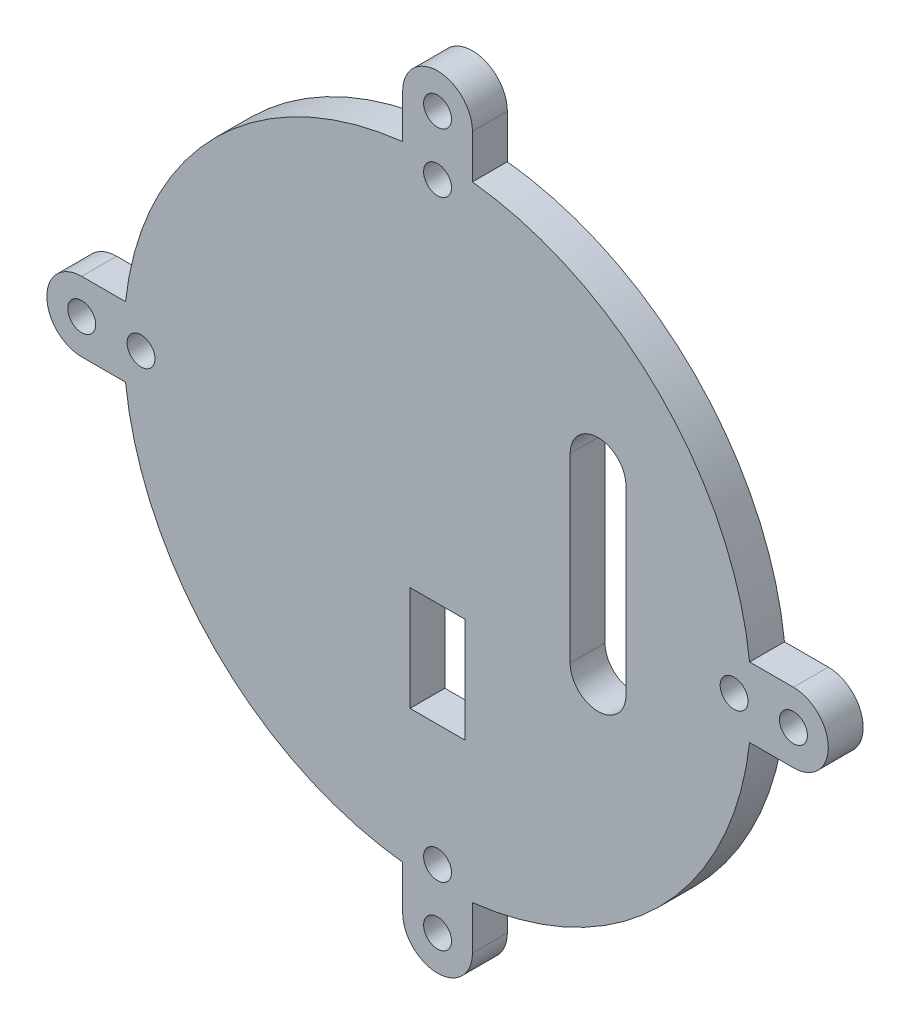
SolidWorks part; units mm, degrees
ref_plane "Front Plane" through (0, 0, 0) normal (0, 0, 1) x (1, 0, 0)
ref_plane "Top Plane" through (0, 0, 0) normal (0, 1, 0) x (1, 0, 0)
ref_plane "Right Plane" through (0, 0, 0) normal (1, 0, 0) x (0, 0, -1)
sketch "Sketch1" plane through (0, 0, 0) normal (0, 0, 1) x (1, 0, 0)
  line L0 (0, 61.1562) -> (0, -62.0155) construction
  line L1 (-62.9195, 0) -> (73.7046, 0) construction
  line L2 (-5, 51) -> (-5, 44.7214)
  line L3 (5, 51) -> (5, 44.7214)
  line L4 (51, 5) -> (44.7214, 5)
  line L5 (51, -5) -> (44.7214, -5)
  line L6 (5, -51) -> (5, -44.7214)
  line L7 (-5, -51) -> (-5, -44.7214)
  line L8 (-51, -5) -> (-44.7214, -5)
  line L9 (-51, 5) -> (-44.7214, 5)
  circle A0 centre (0, 0) radius 45
  circle A1 centre (42.5, 0) radius 2
  circle A2 centre (0, -42.5) radius 2
  circle A3 centre (-42.5, 0) radius 2
  circle A4 centre (0, 42.5) radius 2
  circle A5 centre (0, 0) radius 42.5 construction
  circle A6 centre (0, 51) radius 2
  arc A7 (5, 51) -> (-5, 51) centre (0, 51) ccw
  circle A8 centre (51, 0) radius 2
  arc A9 (51, -5) -> (51, 5) centre (51, 0) ccw
  circle A10 centre (0, -51) radius 2
  arc A11 (-5, -51) -> (5, -51) centre (0, -51) ccw
  circle A12 centre (-51, 0) radius 2
  arc A13 (-51, 5) -> (-51, -5) centre (-51, 0) ccw
  dimension "D1" = 90
  dimension "D5" = 5
  dimension "D2" = 4
  dimension "D3" = 85
  dimension "D4" = 10
extrude "Boss-Extrude1" add sketch "Sketch1" along normal blind 5 contours A0 A4 A3 A2 A1 | L3 A7 L2 A0 A6 | L9 A13 L8 A0 A12 | L5 A9 L4 A0 A8 | L7 A11 L6 A0 A10 region at (0, 55.8493, 0) region at (0, 0, 0) region at (-45.1507, 0, 0) region at (47.8607, 4.8493, 0) region at (0, -45.1507, 0)
sketch "Sketch2" plane through (0, 0, 0) normal (0, 0, -1) x (-1, 0, 0)
  line L1 (-3.95, -10.1) -> (3.95, -10.1)
  line L2 (-3.95, -10.1) -> (-3.95, -25.1)
  line L3 (-3.95, -25.1) -> (3.95, -25.1)
  line L4 (3.95, -10.1) -> (3.95, -25.1)
  point P4 (0, -10.1)
  dimension "D1" = 7.9
  dimension "D2" = 15
  dimension "D3" = 10.1
extrude "Cut-Extrude1" cut sketch "Sketch2" against normal blind 10
sketch "Sketch3" plane through (0, 0, 0) normal (0, 0, -1) x (-1, 0, 0)
  line L0 (-23, 18) -> (-23, -8) construction
  line L1 (-19, 18) -> (-19, -8)
  line L2 (-27, 18) -> (-27, -8)
  arc A0 (-19, 18) -> (-27, 18) centre (-23, 18) ccw
  arc A1 (-27, -8) -> (-19, -8) centre (-23, -8) ccw
  point P2 (-23, 5)
  dimension "D2" = 4
  dimension "D4" = 18
  dimension "D1" = 23
  dimension "D3" = 5
extrude "Cut-Extrude2" cut sketch "Sketch3" against normal blind 10
ref_axis "Axis1" through (0, -51, 5) along (0, 0, -1)
